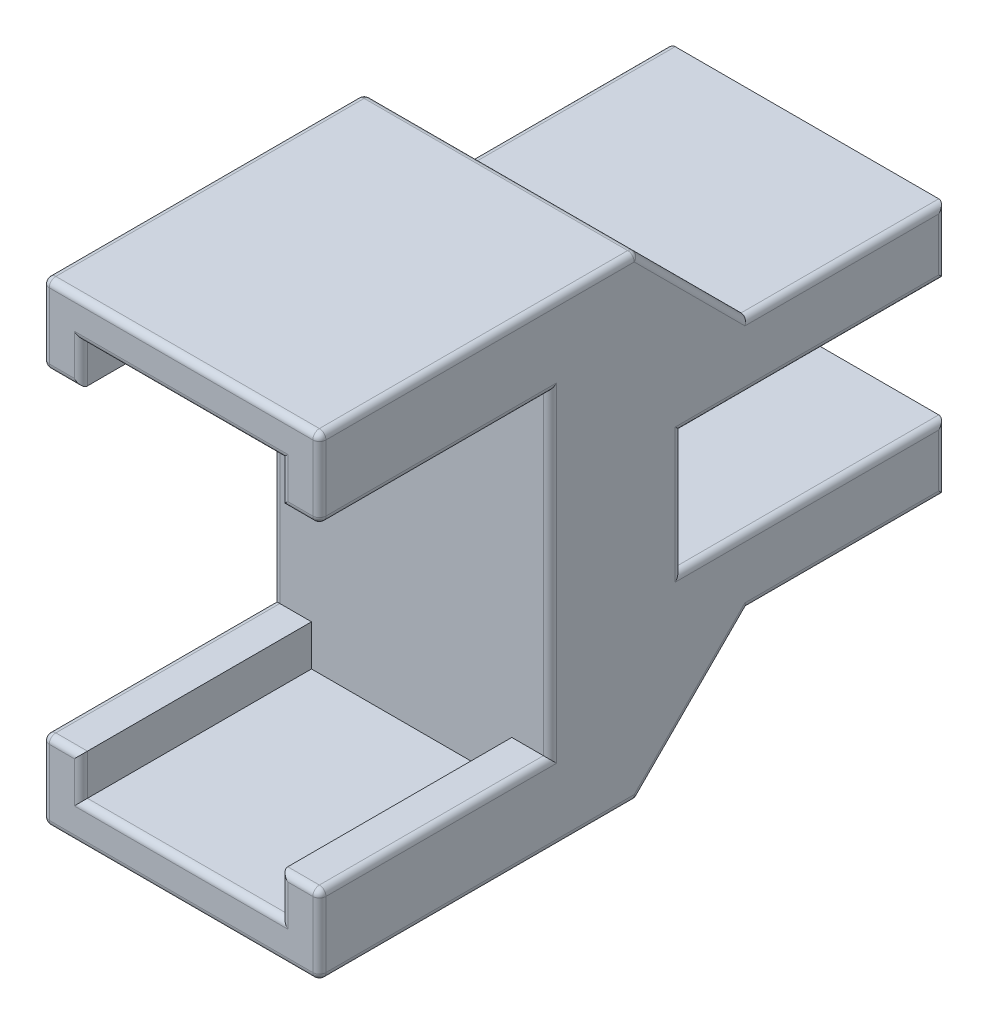
SolidWorks part; units mm, degrees
ref_plane "Front Plane" through (0, 0, 0) normal (0, 0, 1) x (1, 0, 0)
ref_plane "Top Plane" through (0, 0, 0) normal (0, 1, 0) x (1, 0, 0)
ref_plane "Right Plane" through (0, 0, 0) normal (1, 0, 0) x (0, 0, -1)
sketch "Sketch1" plane through (0, 0, 0) normal (1, 0, 0) x (0, 0, -1)
  line L0 (0, 0) -> (111.8919, 0) construction
  line L1 (0, -9.2) -> (0, 9.2)
  line L2 (0, 9.2) -> (40, 9.2)
  line L3 (0, -9.2) -> (40, -9.2)
  line L4 (-10, -19.2) -> (40, -19.2)
  line L5 (-10, -19.2) -> (-10, 19.2)
  line L6 (-10, 19.2) -> (40, 19.2)
  line L7 (40, -9.2) -> (40, -19.2)
  line L8 (40, 9.2) -> (40, 19.2)
  dimension "D1" = 40
  dimension "D2" = 18.4
  dimension "D3" = 10
extrude "Boss-Extrude1" add sketch "Sketch1" along normal mid plane 42
sketch "Sketch2" plane through (0, 0, 10) normal (0, 0, 1) x (1, 0, 0)
  line L0 (-21, 36) -> (21, 36)
  line L1 (-15, 30) -> (15, 30) construction
  line L2 (-15, 30) -> (-15, -30) construction
  line L3 (-15, -30) -> (15, -30) construction
  line L4 (15, 30) -> (15, -30) construction
  line L5 (-15, 30) -> (15, -30) construction
  line L6 (-15, -30) -> (15, 30) construction
  line L7 (21, 36) -> (21, -36)
  line L8 (-21, -36) -> (21, -36)
  line L9 (-21, 36) -> (-21, -36)
  point P0 (0, 0)
  dimension "D1" = 30
  dimension "D2" = 60
  dimension "D3" = 6
extrude "Boss-Extrude2" add sketch "Sketch2" along normal blind 10
sketch "Sketch3" plane through (0, 0, 20) normal (0, 0, 1) x (1, 0, 0)
  line L0 (-15.2, 30.2) -> (-15.2, 24)
  line L1 (-15, 30) -> (15, 30) construction
  line L2 (-15, 30) -> (-15, -30) construction
  line L3 (-15, -30) -> (15, -30) construction
  line L4 (15, 30) -> (15, -30) construction
  line L5 (-15, 30) -> (15, -30) construction
  line L6 (-15, -30) -> (15, 30) construction
  line L7 (-15.2, -30.2) -> (15.2, -30.2)
  line L8 (15.2, 30.2) -> (15.2, 24)
  line L9 (-15.2, 30.2) -> (15.2, 30.2)
  line L11 (-21, -24) -> (-15.2, -24)
  line L12 (-21, 0) -> (21, 0) construction
  line L13 (-21, 24) -> (-15.2, 24)
  line L14 (-21, -24) -> (-21, -36)
  line L15 (-21, 36) -> (-21, -36)
  line L16 (-21, -36) -> (21, -36)
  line L17 (21, -36) -> (21, 36)
  line L18 (21, 36) -> (-21, 36)
  line L19 (-21, 36) -> (-21, 24)
  line L20 (-21, -36) -> (21, -36)
  line L21 (21, -36) -> (21, -24)
  line L22 (21, 36) -> (-21, 36)
  line L23 (21, 24) -> (21, 36)
  line L24 (15.2, 24) -> (21, 24)
  line L25 (15.2, -24) -> (15.2, -30.2)
  line L26 (15.2, -24) -> (21, -24)
  line L27 (-15.2, -24) -> (-15.2, -30.2)
  line L28 (15.2, 30.2) -> (15.2, -30.2) construction
  line L30 (-15.2, 30.2) -> (-15.2, -30.2) construction
  point P0 (0, 0)
  point P21 (-15, 20.9947)
  dimension "D1" = 30
  dimension "D2" = 60
  dimension "D5" = 12
  dimension "D6" = 12
  dimension "D3" = 0.2
  dimension "D4" = 0
extrude "Boss-Extrude3" add sketch "Sketch3" along normal blind 35
chamfer "Chamfer1" distance 20 angle 45 2 edges at (0, -19.2, 10) (0, 19.2, 10)
fillet "Fillet1" radius 1 46 edges at (-21, 19.2, -25) (-21, 24, 37.5) (-21, 0, 20) (-21, -24, 37.5) (-21, -36, 30.9) (-21, -19.2, -25) (-21, -14.2, -40) (-21, -9.2, -20) (-21, 0, 0) (-21, 9.2, -20) (-21, 14.2, -40) (21, 9.2, -20) (21, 0, 0) (21, -9.2, -20) (21, -14.2, -40) (21, -19.2, -25) (21, -36, 30.9) (21, -24, 37.5) (21, 0, 20) (21, 24, 37.5) (21, 19.2, -25) (21, 14.2, -40) (21, 36, 30.9) (-21, 36, 30.9) (-15.2, 27.1, 55) (-18.1, 24, 55) (-21, 30, 55) (0, 36, 55) (21, 30, 55) (18.1, 24, 55) (15.2, 27.1, 55) (0, 30.2, 55) (0, -30.2, 55) (15.2, -27.1, 55) (18.1, -24, 55) (21, -30, 55) (0, -36, 55) (-21, -30, 55) (-18.1, -24, 55) (-15.2, -27.1, 55) (0, -36, 6.8) (-21, 27.6, -1.6) (-21, -27.6, -1.6) (21, -27.6, -1.6) (21, 27.6, -1.6) (0, 36, 6.8)
